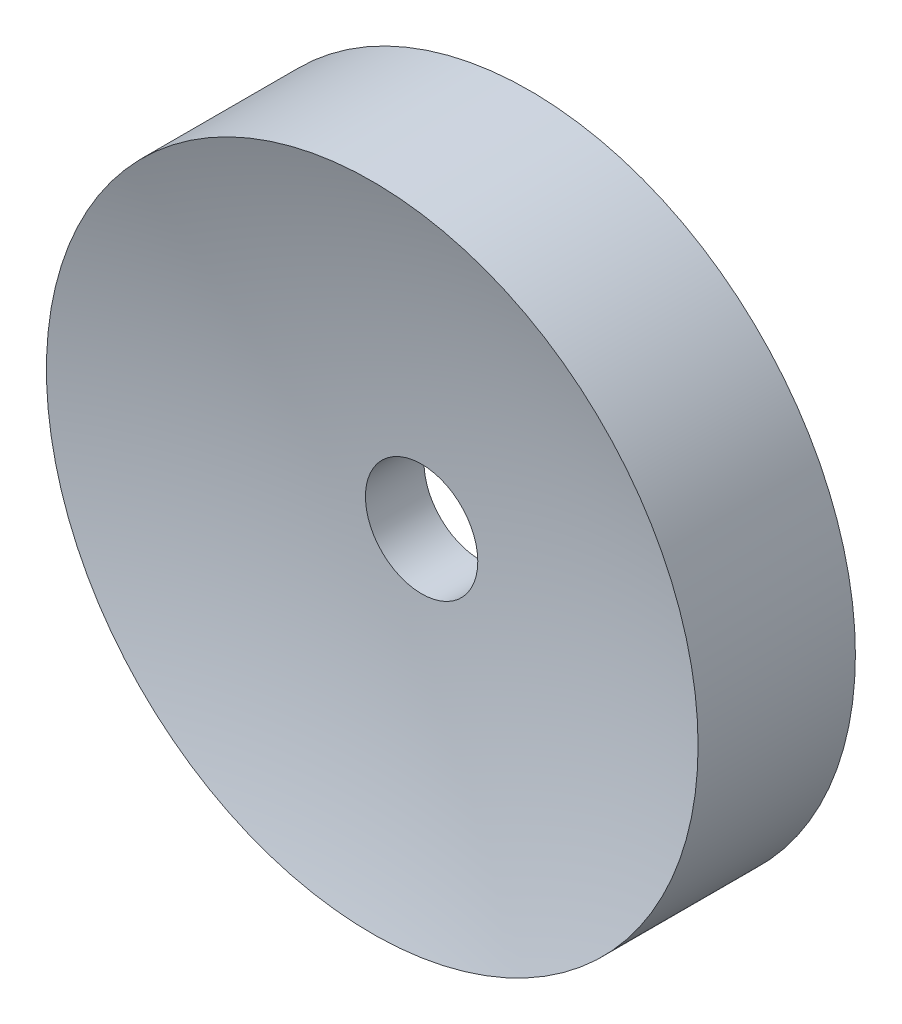
SolidWorks part; units mm, degrees
ref_plane "Front Plane" through (0, 0, 0) normal (0, 0, 1) x (1, 0, 0)
ref_plane "Top Plane" through (0, 0, 0) normal (0, 1, 0) x (1, 0, 0)
ref_plane "Right Plane" through (0, 0, 0) normal (1, 0, 0) x (0, 0, -1)
sketch "Sketch1" plane through (0, 0, 0) normal (0, 0, 1) x (1, 0, 0)
  line L0 (0, -7.25) -> (0, 7.25) construction
  circle A0 centre (0, 0) radius 1.25
  circle A1 centre (0, 0) radius 7.25
  point P7 (0, 0)
  dimension "D2" = 2.5
  dimension "D1" = 6
extrude "Boss-Extrude1" add sketch "Sketch1" along normal mid plane 3.5
sketch "Sketch2" plane through (0, 0, 0) normal (0, 1, 0) x (1, 0, 0)
  line L0 (-7.25, 1.75) -> (-7.25, -1.75) construction
  line L2 (-7.25, 1.75) -> (7.25, 1.75)
  line L3 (0, 3.9821) -> (0, -0.4821) construction
  arc A0 (7.25, 1.75) -> (-7.25, 1.75) centre (0, 24.4221) cw
  point P9 (0, 1.75)
  dimension "D1" = 23.8031
ref_axis "Axis1" through (0, 0, 1.75) along (0, 0, -1)
revolve "Cut-Revolve1" cut sketch "Sketch2" angle 360 about L3 region at (-2.7276, 0, -1.2967)
mirror "Mirror1" about plane through (0, 0, 0) normal (0, 0, 1) of "Cut-Revolve1"
